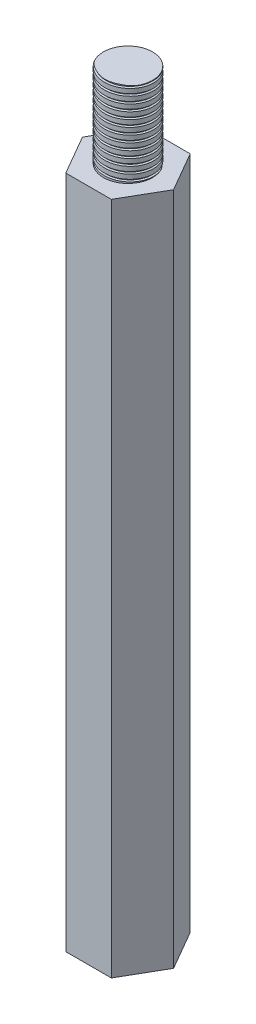
SolidWorks part; units mm, degrees
note: The reader was unsure of these and kept them because the rebuilt part matched: shared geometry of "草图1<3>".
ref_plane "前视基准面" through (0, 0, 0) normal (0, 0, 1) x (1, 0, 0)
ref_plane "上视基准面" through (0, 0, 0) normal (0, 1, 0) x (1, 0, 0)
ref_plane "右视基准面" through (0, 0, 0) normal (1, 0, 0) x (0, 0, -1)
sketch "草图1" plane through (0, 0, 0) normal (0, 1, 0) x (1, 0, 0)
  line L0 (0, 0) -> (0, 4.5761) construction
  line L1 (1.351, -2.34) -> (2.702, 0)
  line L2 (2.702, 0) -> (1.351, 2.34)
  line L3 (1.351, 2.34) -> (-1.351, 2.34)
  line L4 (-1.351, 2.34) -> (-2.702, 0)
  line L5 (-2.702, 0) -> (-1.351, -2.34)
  line L6 (-1.351, -2.34) -> (1.351, -2.34)
  line L7 (0, 4.5761) -> (0, -3.6794) construction
  circle A0 centre (0, 0) radius 2.34 construction
  circle A1 centre (0, 0) radius 1.46
  dimension "D1" = 4.68
  dimension "D2" = 2.92
extrude "凸台-拉伸1" add sketch "草图1" along normal blind 40 contours A1 | L5 L6 L1 L2 L3 L4 A1
extrude "切除-拉伸1" cut sketch "草图1<3>" along normal blind 5 contours A1
sketch "草图1<3>" plane through (0, 0, 0) normal (0, 1, 0) x (1, 0, 0) same geometry as "草图1"
sketch "草图2" plane through (0, 40, 0) normal (0, 1, 0) x (1, 0, 0)
  circle A0 centre (0, 0) radius 1.46
  dimension "D1" = 2.92
extrude "凸台-拉伸2" add sketch "草图2" along normal blind 5 separate body
ref_plane "基准面1" through (0, 0, 0) normal (0, 0, -1) x (-1, 0, 0)
sketch "草图4" plane through (0, 0, 0) normal (0, 0, -1) x (-1, 0, 0)
  line L0 (0, 0) -> (0, 28.5702) construction
  line L1 (-1.56, 40) -> (-1.56, 40.2)
  line L2 (-1.56, 40.2) -> (-1.36, 40.1333)
  line L3 (-1.36, 40.0667) -> (-1.56, 40)
  line L4 (-1.26, 40.1) -> (-2.0659, 40.1) construction
  line L5 (-2.0659, 40.1) -> (-0.8933, 40.1) construction
  line L7 (-1.46, 45) -> (-1.46, 40) construction
  line L8 (-1.36, 40.1333) -> (-1.36, 40.0667)
  line L9 (-1.46, 40) -> (1.46, 40) construction
  dimension "D1" = 0.1
  dimension "D2" = 0.1
  dimension "D3" = 0.1
  dimension "D4" = 0.3
  dimension "D5" = 0.2
  dimension "D6" = 0.1
  dimension "D7" = 0.0667
  dimension "D8" = 0.0667
ref_plane "基准面2" through (0, 40.1, 0) normal (0, 1, 0) x (1, 0, 0)
sketch "草图5" plane through (0, 40.1, 0) normal (0, 1, 0) x (1, 0, 0)
  circle A0 centre (0, 0) radius 1.46
  dimension "D1" = 2.92
curve "螺旋线/涡状线1" pitch 0.4 height 7.5 turns 18.75
sweep "切除-扫描1" cut profiles "草图4" path "螺旋线/涡状线1"
sketch "草图6" plane through (0, 0, 0) normal (0, -1, 0) x (1, 0, 0)
  circle A0 centre (0, 0) radius 1.46
curve "螺旋线/涡状线2" pitch 0.4 height 9.5 turns 23.75
sketch "草图7" plane through (0, 0, 0) normal (0, 0, -1) x (-1, 0, 0)
  line L0 (1.46, 0.2) -> (1.66, 0.1333)
  line L1 (1.66, 0.0667) -> (1.46, 0)
  line L2 (1.46, 0.2) -> (1.46, 0)
  line L3 (1.66, 0.1333) -> (1.66, 0.0667)
  line L8 (1.351, 0) -> (-1.351, 0) construction
  dimension "D1" = 0.2
  dimension "D3" = 1.46
  dimension "D4" = 0.2
sweep "切除-扫描2" cut profiles "草图7" path "螺旋线/涡状线2"
equation "\"chang\"= 20mm"
equation "\"r\"= 2.92mm"
equation "\"luowengao\"= 6.5mm"
equation "\"rr\"= 4.68mm"
equation "\"D1@草图1\"=\"rr\""
equation "\"D2@草图1\"=\"r\""
equation "\"D1@凸台-拉伸1\"=\"chang\""
equation "\"D1@切除-拉伸1\"=\"luowengao\"+5mm"
equation "\"D1@草图2\"=\"r\""
equation "\"D1@凸台-拉伸2\"=\"luowengao\""
